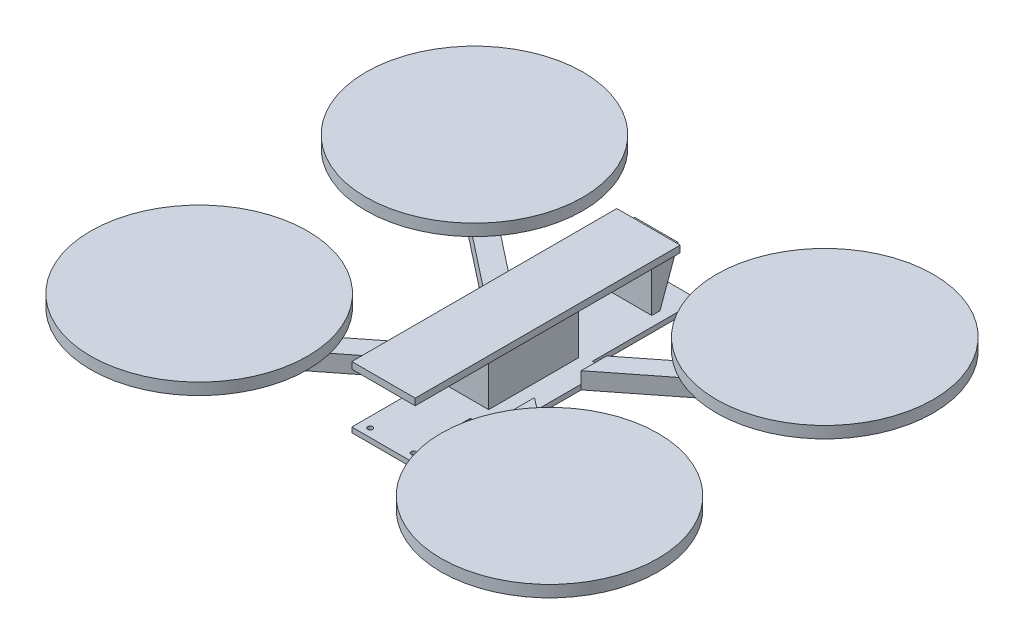
SolidWorks part; units mm, degrees
note: The reader was unsure of these and kept them because the rebuilt part matched: shared geometry of "Sketch2<3>", "Sketch2<4>".
ref_plane "前视基准面" through (0, 0, 0) normal (0, 0, 1) x (1, 0, 0)
ref_plane "上视基准面" through (0, 0, 0) normal (0, 1, 0) x (1, 0, 0)
ref_plane "右视基准面" through (0, 0, 0) normal (1, 0, 0) x (0, 0, -1)
other "Configuration Table"
sketch "Sketch2" plane through (0, 0, 0) normal (0, 1, 0) x (1, 0, 0)
  line L0 (-105, 82.5) -> (-24.3034, 19.0955)
  line L1 (-19, 93) -> (19, 93)
  line L2 (-19, 93) -> (-19, -77)
  line L3 (-19, -77) -> (19, -77)
  line L4 (19, 93) -> (19, -77)
  line L5 (-105, 82.5) -> (105, 82.5)
  line L6 (-105, 82.5) -> (-105, -82.5)
  line L7 (-105, -82.5) -> (105, -82.5)
  line L8 (105, 82.5) -> (105, -82.5)
  line L9 (105, 82.5) -> (24.3034, 19.0955)
  line L10 (-108.7069, 77.7821) -> (-27.5, 13.9766)
  line L11 (101.2931, 87.2179) -> (27.5, 29.2376)
  line L12 (-101.2931, 87.2179) -> (-27.5, 29.2376)
  line L13 (108.7069, 77.7821) -> (27.5, 13.9766)
  line L14 (-19, -72) -> (19, -72)
  line L20 (12, -37) -> (14, -37)
  line L21 (12, -37) -> (12, -43)
  line L22 (12, -43) -> (14, -43)
  line L23 (14, -37) -> (14, -43)
  line L24 (13, -43) -> (13, -37) construction
  line L25 (12, -40) -> (14, -40) construction
  line L26 (-14.417, -37) -> (-12.417, -37)
  line L27 (-14.417, -37) -> (-14.417, -43)
  line L28 (-14.417, -43) -> (-12.417, -43)
  line L29 (-12.417, -37) -> (-12.417, -43)
  line L30 (-13.417, -43) -> (-13.417, -37) construction
  line L31 (-14.417, -40) -> (-12.417, -40) construction
  line L37 (-19, 20) -> (19, 20)
  line L38 (-25.5, 20) -> (-24, 20)
  line L39 (-25.5, 20) -> (-25.5, 18.5)
  line L40 (-25.5, -20) -> (-24, -20)
  line L41 (25.5, 20) -> (25.5, 18.5)
  line L43 (24, -20) -> (25.5, -20)
  line L44 (-27.5, 29.2376) -> (27.5, 29.2376)
  line L45 (-27.5, 29.2376) -> (-27.5, -29.2376)
  line L46 (-27.5, -29.2376) -> (27.5, -29.2376)
  line L47 (27.5, 29.2376) -> (27.5, -29.2376)
  line L48 (0, -29.2376) -> (0, -20) construction
  line L49 (-27.5, 0) -> (-25.5, 0) construction
  line L51 (0, 20) -> (0, 29.2376) construction
  line L52 (24.3034, -19.0955) -> (105, -82.5)
  line L53 (-105, 82.5) -> (105, -82.5) construction
  line L54 (9.7075, -0.0032) -> (9.7156, -0.0032) construction
  line L56 (25.5, 0) -> (27.5, 0) construction
  line L57 (-24.3034, -19.0955) -> (-105, -82.5)
  line L58 (105, 82.5) -> (-105, -82.5) construction
  line L59 (9.7115, 0) -> (9.7156, -0.0032)
  line L60 (-101.2931, 87.2179) -> (108.7069, -77.7821) construction
  line L61 (9.7115, 0) -> (9.7075, -0.0032)
  line L62 (108.7069, 77.7821) -> (-101.2931, -87.2179) construction
  line L64 (27.5, -13.9766) -> (108.7069, -77.7821)
  line L65 (-19, -20) -> (19, -20)
  line L66 (-108.7069, 77.7821) -> (101.2931, -87.2179) construction
  line L67 (-27.5, -29.2376) -> (-101.2931, -87.2179)
  line L68 (-27.5, -13.9766) -> (-108.7069, -77.7821)
  line L69 (101.2931, 87.2179) -> (-108.7069, -77.7821) construction
  line L70 (-9.7156, 0.0032) -> (-9.7075, 0.0032) construction
  line L71 (-9.7156, 0.0032) -> (-9.7115, 0)
  line L72 (-9.7075, 0.0032) -> (-9.7115, 0)
  line L73 (27.5, -29.2376) -> (101.2931, -87.2179)
  line L74 (-25.5, -18.5) -> (-25.5, -20)
  line L76 (24, 20) -> (25.5, 20)
  line L77 (25.5, -18.5) -> (25.5, -20)
  circle A0 centre (-105, 82.5) radius 15
  circle A1 centre (105, 82.5) radius 15
  circle A2 centre (105, -82.5) radius 15
  circle A3 centre (-105, -82.5) radius 15
  circle A4 centre (-13, -72) radius 1.5
  circle A5 centre (13, -72) radius 1.5
  circle A6 centre (-25.5, 20) radius 1.5
  circle A7 centre (25.5, 20) radius 1.5
  circle A8 centre (25.5, -20) radius 1.5
  circle A9 centre (-25.5, -20) radius 1.5
  point P0 (0, 0)
  point P28 (13, -40)
  point P32 (-13.417, -40)
  point P39 (0, 0)
  point P42 (0, 0)
  point P53 (0, 0)
  point P66 (0, 0)
  dimension "D11" = 5
  dimension "D12" = 6
  dimension "D20" = 40
  dimension "D1" = 170
  dimension "D2" = 38
  dimension "D3" = 77
  dimension "D4" = 19
  dimension "D5" = 165
  dimension "D6" = 210
  dimension "D7" = 105
  dimension "D8" = 82.5
  dimension "D9" = 6
  dimension "D13" = 6
  dimension "D14" = 6
  dimension "D15" = 2
  dimension "D16" = 32
  dimension "D17" = 6
  dimension "D18" = 2
  dimension "D19" = 58.4753
  dimension "D21" = 51
  dimension "D22" = 55
  dimension "D10" = 6
extrude "Boss-Extrude2" add sketch "Sketch2" along normal blind 3
extrude "Boss-Extrude3" add sketch "Sketch2<3>" along normal blind 10 contours A3 L9 L2 L11 | A3 L13 L2 L9 | A2 L12 L4 L0 | A2 L0 L4 L10 | A1 L11 L4 L9 | A1 L9 L4 L13 | A0 L10 L2 L0 | A0 L0 L2 L12
sketch "Sketch2<3>" plane through (0, 0, 0) normal (0, 1, 0) x (1, 0, 0) same geometry as "Sketch2"
extrude "Boss-Extrude4" add sketch "Sketch2<4>" along normal blind 25 contours A0 | A1 | A2 | A3
sketch "Sketch2<4>" plane through (0, 0, 0) normal (0, 1, 0) x (1, 0, 0) same geometry as "Sketch2"
sketch "Sketch3" plane through (0, 25, 0) normal (0, 1, 0) x (1, 0, 0)
  circle A0 centre (-105, -82.5) radius 65
  circle A1 centre (105, -82.5) radius 65
  circle A2 centre (105, 82.5) radius 65
  circle A3 centre (-105, 82.5) radius 65
extrude "Boss-Extrude5" add sketch "Sketch3" along normal blind 7
sketch "Sketch4" plane through (0, 3, 0) normal (0, 1, 0) x (1, 0, 0)
  line L1 (-13, 27) -> (13, 27)
  line L2 (-13, 27) -> (-13, -27)
  line L3 (-13, -27) -> (13, -27)
  line L4 (13, 27) -> (13, -27)
  line L5 (0, -27) -> (0, 27) construction
  line L6 (-13, 0) -> (13, 0) construction
  line L7 (-13, 86.6083) -> (13, 86.6083)
  line L8 (-13, 86.6083) -> (-13, 70.7505)
  line L9 (-13, 70.7505) -> (13, 70.7505)
  line L10 (13, 86.6083) -> (13, 70.7505)
  line L11 (0, 70.7505) -> (0, 86.6083) construction
  line L12 (-13, 78.6794) -> (13, 78.6794) construction
  point P0 (0, 0)
  point P4 (0, 78.6794)
  dimension "D1" = 54
  dimension "D2" = 26
  dimension "D3" = 15.8578
  dimension "D4" = 26
extrude "Boss-Extrude6" add sketch "Sketch4" along normal blind 30
sketch "Sketch5" plane through (0, 33, 0) normal (0, 1, 0) x (1, 0, 0)
  line L15 (-19, -77) -> (19, -77)
  line L16 (-19, -77) -> (-19, 81.8144)
  line L17 (-19, 81.8144) -> (19, 81.8144)
  line L18 (19, -77) -> (19, 81.8144)
  line L19 (19, 93) -> (19, 29.2376) construction
  dimension "D1" = 158.8144
  dimension "D2" = 38
extrude "Boss-Extrude7" add sketch "Sketch5" along normal blind 4
draft "Draft1" type of draft neutral plane draft angle 20 faces to draft 1 face at (0, 18, -86.6083) neutral plane through (0, 33, 0) neutral plane normal (0, 1, 0) reverse direction yes parameters "D1"=20
sketch "Sketch6" plane through (0, 0, 0) normal (0, -1, 0) x (1, 0, 0)
  circle A0 centre (0, 0) radius 0.5
extrude "Cut-Extrude1" cut sketch "Sketch6" against normal blind 1
